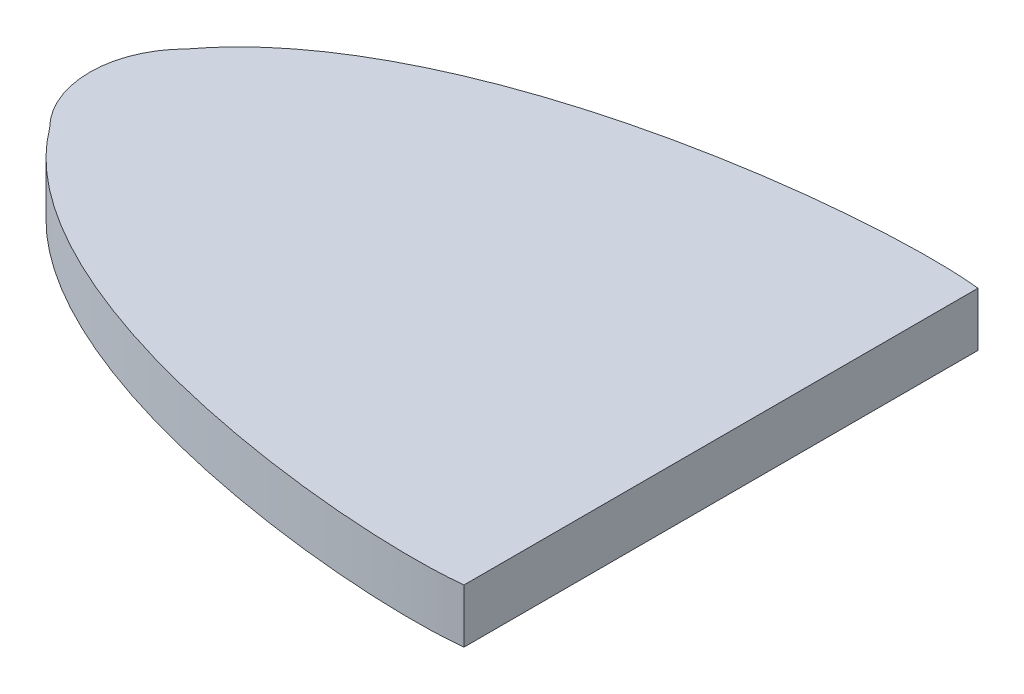
SolidWorks part; units mm, degrees
ref_plane "Front Plane" through (0, 0, 0) normal (0, 0, 1) x (1, 0, 0)
ref_plane "Top Plane" through (0, 0, 0) normal (0, 1, 0) x (1, 0, 0)
ref_plane "Right Plane" through (0, 0, 0) normal (1, 0, 0) x (0, 0, -1)
sketch "Sketch1" plane through (0, 0, 0) normal (0, 1, 0) x (1, 0, 0)
  line L0 (-45.7896, 0) -> (47.7286, 0) construction
  line L1 (0, 37.1388) -> (0, -23.1185) construction
  line L2 (-55.9, 0) -> (-55.9, 29.9795) construction
  line L3 (24, 0) -> (24, 21.4779) construction
  line L4 (-46.9, 9) -> (-46.9, -9) construction
  line L5 (-46.9, 0) -> (-53.264, 6.364) construction
  line L6 (2.6813, -23.8497) -> (2.6813, 23.8497)
  circle A0 centre (-46.9, 0) radius 9
  circle A1 centre (0, 0) radius 24
  spline S0 degree 3 poles (-53.264, 6.364) (-41.9045, 21.6052) (-7.8082, 25.0296) (2.6813, 23.8497) knots 0 0 0 0 1 1 1 1
  spline S1 degree 3 poles (-53.264, -6.364) (-41.9045, -21.6052) (-7.8082, -25.0296) (2.6813, -23.8497) knots 0 0 0 0 1 1 1 1
  dimension "D1" = 48
  dimension "D3" = 18
  dimension "D2" = 79.9
  dimension "D4" = 45
extrude "Boss-Extrude1" add sketch "Sketch1" along normal blind 5 contours A0 | A0 S1 A1 S0 | L6 A1 region at (-8.7533, 0, 0) region at (-29.9551, 0, 0) region at (-46.9, 0, 0)
